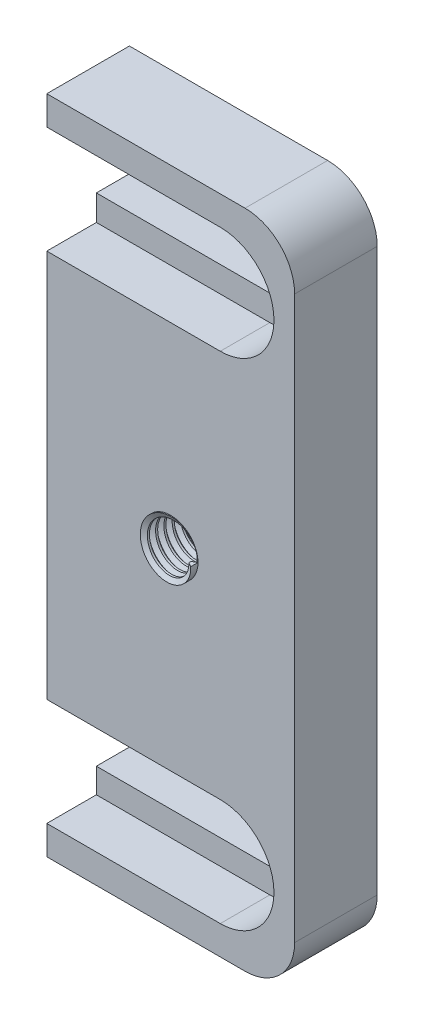
SolidWorks part; units mm, degrees
ref_plane "Front Plane" through (0, 0, 0) normal (0, 0, 1) x (1, 0, 0)
ref_plane "Top Plane" through (0, 0, 0) normal (0, 1, 0) x (1, 0, 0)
ref_plane "Right Plane" through (0, 0, 0) normal (1, 0, 0) x (0, 0, -1)
ref_plane "Plane1" through (0, 0, 5) normal (0, 0, 1) x (1, 0, 0)
sketch "Sketch1" plane through (0, 0, 5) normal (0, 0, 1) x (1, 0, 0)
  line L0 (15, 0) -> (0, 0)
  line L1 (0, 0) -> (0, -40)
  line L2 (0, -40) -> (15, -40)
  line L3 (15, -40) -> (15, 0)
extrude "Boss-Extrude1" add sketch "Sketch1" against normal blind 5
sketch "Sketch2" plane through (0, 0, 5) normal (0, 0, 1) x (1, 0, 0)
  line L0 (0, -8.25) -> (10.5, -8.25)
  line L1 (10.5, -1.75) -> (0, -1.75)
  line L2 (0, -1.75) -> (0, -8.25)
  arc A0 (10.5, -8.25) -> (10.5, -1.75) centre (10.5, -5) ccw
extrude "Cut-Extrude1" cut sketch "Sketch2" against normal blind 3
sketch "Sketch3" plane through (0, 0, 2) normal (0, 0, 1) x (1, 0, 0)
  line L0 (0, -3.3) -> (0, -6.7)
  line L1 (0, -6.7) -> (10.5, -6.7)
  line L2 (10.5, -3.3) -> (0, -3.3)
  arc A0 (10.5, -6.7) -> (10.5, -3.3) centre (10.5, -5) ccw
extrude "Cut-Extrude2" cut sketch "Sketch3" against normal through all
sketch "Sketch4" plane through (0, 0, 5) normal (0, 0, 1) x (1, 0, 0)
  line L0 (0, -38.25) -> (10.5, -38.25)
  line L1 (10.5, -31.75) -> (0, -31.75)
  line L2 (0, -31.75) -> (0, -38.25)
  arc A0 (10.5, -38.25) -> (10.5, -31.75) centre (10.5, -35) ccw
extrude "Cut-Extrude3" cut sketch "Sketch4" against normal blind 3
sketch "Sketch5" plane through (0, 0, 0) normal (0, 0, -1) x (-1, 0, 0)
  line L0 (0, -36.75) -> (0, -33.25)
  line L1 (0, -33.25) -> (-10.5, -33.25)
  line L2 (-10.5, -36.75) -> (0, -36.75)
  arc A0 (-10.5, -33.25) -> (-10.5, -36.75) centre (-10.5, -35) ccw
extrude "Cut-Extrude4" cut sketch "Sketch5" against normal through all
hole_wizard "#4 Clearance Hole1" positions "Sketch7" profile "Sketch6" hole size "#4" standard "ANSI Inch"
sketch "Sketch7" plane through (0, 0, 5) normal (0, 0, 1) x (1, 0, 0)
  point P0 (7.5, -20)
sketch "Sketch6" plane through (7.5, -20, 5) normal (1, 0, 0) x (0, -1, 0)
  line L0 (0, 0) -> (0, 5)
  line L1 (0, 5) -> (1.65, 5)
  line L2 (1.65, 5) -> (1.65, 0)
  line L5 (1.65, 0) -> (0, 0)
  line L11 (0, -6.35) -> (0, 107.95) construction
  dimension "Thru Hole Dia." = 3.3
  dimension "Thru Hole Depth" = 5
fillet "Fillet1" radius 3 2 edges at (15, -40, 2.5) (15, 0, 2.5) tangent propagation no
thread "螺纹线1" pitch 0.5 method extrude profile "螺纹线轮廓2" start angle 0, offset 0, length 5, pitch 0.5, diameter 3.3
ref_plane "基准面2" through (9.15, -20, 0) normal (0, -1, 0) x (1, 0, 0)
sketch "螺纹线轮廓2" plane through (9.15, -20, 0) normal (0, -1, 0) x (1, 0, 0)
  line L0 (0, 0) -> (0, 0.5) construction
  line L11 (0, 0) -> (0, 0.4375)
  line L12 (0, 0.4375) -> (-0.2706, 0.2812)
  line L13 (-0.2706, 0.2812) -> (-0.2706, 0.1562)
  line L15 (-0.2706, 0.1562) -> (0, 0)
  line L17 (-0.2706, 0.2187) -> (0, 0.2187) construction
  point P2 (0, 0)
  dimension "Pitch" = 0.5
  dimension "Profile_Angle" = 60
  dimension "Profile_Land" = 0.125
  dimension "Profile_Height" = 0.2706
